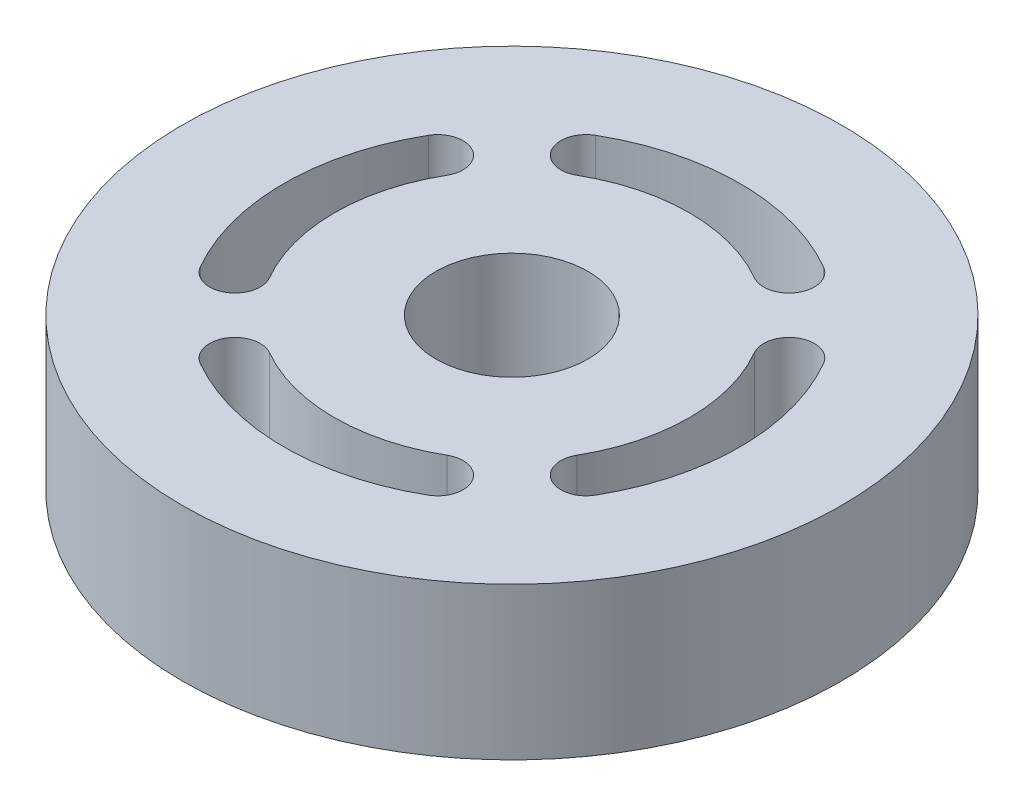
SolidWorks part; units mm, degrees
ref_plane "Front Plane" through (0, 0, 0) normal (0, 0, 1) x (1, 0, 0)
ref_plane "Top Plane" through (0, 0, 0) normal (0, 1, 0) x (1, 0, 0)
ref_plane "Right Plane" through (0, 0, 0) normal (1, 0, 0) x (0, 0, -1)
sketch "Sketch1" plane through (0, 0, 0) normal (0, 1, 0) x (1, 0, 0)
  line L0 (0, 0) -> (0, 14.568) construction
  circle A0 centre (0, 0) radius 13
  circle A1 centre (0, 0) radius 3
  arc A2 (-3.5, 6.0622) -> (0, 7) centre (0, 0) cw
  arc A3 (-4.5, 7.7942) -> (0, 9) centre (0, 0) cw
  arc A4 (-3.5, 6.0622) -> (-4.5, 7.7942) centre (-4, 6.9282) cw
  arc A5 (3.5, 6.0622) -> (0, 7) centre (0, 0) ccw
  arc A6 (3.5, 6.0622) -> (4.5, 7.7942) centre (4, 6.9282) ccw
  arc A7 (4.5, 7.7942) -> (0, 9) centre (0, 0) ccw
  point P8 (-4.0195, 6.9169)
  dimension "D1" = 6
  dimension "D2" = 26
  dimension "D3" = 7
  dimension "D5" = 4
  dimension "D4" = 2
extrude "Boss-Extrude1" add sketch "Sketch1" along normal blind 6
pattern_circular "CirPattern1" count 4 over 360 about axis through (0, 6, 0) along (0, 1, 0) of face at (0, 3, -8.3971) of face at (0, 3, -6.5311) of face at (4.433, 3, -6.6782) of face at (-4.433, 3, -6.6782)
